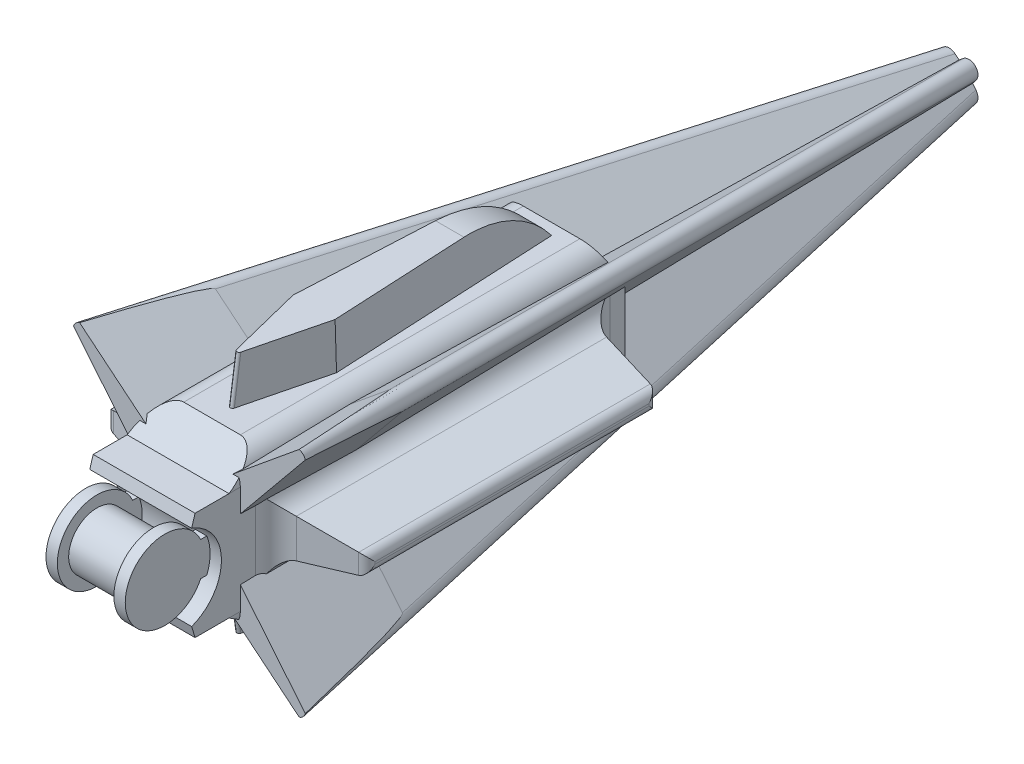
SolidWorks part; units mm, degrees
ref_plane "Front Plane" through (0, 0, 0) normal (0, 0, 1) x (1, 0, 0)
ref_plane "Top Plane" through (0, 0, 0) normal (0, 1, 0) x (1, 0, 0)
ref_plane "Right Plane" through (0, 0, 0) normal (1, 0, 0) x (0, 0, -1)
sketch "Sketch1" plane through (0, 0, 0) normal (1, 0, 0) x (0, 0, -1)
  circle A0 centre (0, 0) radius 3.175
  dimension "D1" = 6.35
extrude "Boss-Extrude1" add sketch "Sketch1" along normal mid plane 6.35
sketch "Sketch2" plane through (3.175, 0, 0) normal (1, 0, 0) x (0, 0, -1)
  circle A0 centre (0, 0) radius 4.445
  dimension "D1" = 8.89
extrude "Boss-Extrude2" add sketch "Sketch2" along normal blind 1.27
mirror "Mirror1" about plane through (0, 0, 0) normal (1, 0, 0) of "Boss-Extrude2"
sketch "Sketch3" plane through (4.445, 0, 0) normal (1, 0, 0) x (0, 0, -1)
  line L1 (0, 1.905) -> (6.35, 1.905)
  line L2 (0, 1.905) -> (0, -1.905)
  line L3 (0, -1.905) -> (6.35, -1.905)
  line L4 (6.35, 1.905) -> (6.35, -1.905)
  point P4 (0, 0)
  dimension "D1" = 3.81
  dimension "D2" = 6.35
extrude "Boss-Extrude3" add sketch "Sketch3" against normal blind 1.27
mirror "Mirror2" about plane through (0, 0, 0) normal (1, 0, 0) of "Boss-Extrude3"
sketch "Sketch4" plane through (-3.175, 0, 0) normal (1, 0, 0) x (0, 0, -1)
  line L0 (1.7375, 4.7736) -> (0, 0) construction
  line L1 (0, 0) -> (5.08, 0) construction
  line L2 (1.7375, 4.7736) -> (2.1185, 6.0436)
  line L3 (2.1185, 6.0436) -> (5.9285, 6.0436)
  line L4 (0, 0) -> (1.7375, -4.7736) construction
  line L5 (5.9285, 6.0436) -> (9.7385, 8.5836)
  line L6 (9.7385, 8.5836) -> (47.8385, 8.5836)
  line L7 (47.8385, 8.5836) -> (50.3785, 3.81)
  line L8 (50.3785, 3.81) -> (50.3785, -3.81)
  line L9 (50.3785, 0) -> (5.08, 0) construction
  line L10 (47.8385, -8.5836) -> (50.3785, -3.81)
  line L11 (9.7385, -8.5836) -> (47.8385, -8.5836)
  line L12 (5.9285, -6.0436) -> (9.7385, -8.5836)
  line L13 (2.1185, -6.0436) -> (5.9285, -6.0436)
  line L14 (1.7375, -4.7736) -> (2.1185, -6.0436)
  arc A0 (1.7375, 4.7736) -> (1.7375, -4.7736) centre (0, 0) cw
  dimension "D1" = 5.08
  dimension "D2" = 140
  dimension "D3" = 1.27
  dimension "D4" = 0.381
  dimension "D5" = 3.81
  dimension "D6" = 3.81
  dimension "D7" = 2.54
  dimension "D8" = 38.1
  dimension "D9" = 7.62
  dimension "D10" = 2.54
extrude "Boss-Extrude4" add sketch "Sketch4" against normal blind 2.54 and the other way blind 8.89
sketch "Sketch5" plane through (0, 0, -50.3785) normal (0, 0, -1) x (-1, 0, 0)
  circle A0 centre (0, 0) radius 3.175
  dimension "D1" = 6.35
extrude "Cut-Extrude1" cut sketch "Sketch5" against normal blind 12.7
fillet "Fillet1" radius 2.54 4 edges at (5.715, -8.5836, -28.7885) (-5.715, -8.5836, -28.7885) (-5.715, 8.5836, -28.7885) (5.715, 8.5836, -28.7885)
sketch "Sketch6" plane through (5.715, 0, 0) normal (1, 0, 0) x (0, 0, -1)
  line L0 (50.3785, -3.81) -> (50.3785, 3.81) construction
  line L1 (11.0085, 2.54) -> (46.5685, 2.54)
  line L2 (11.0085, 2.54) -> (11.0085, -2.54)
  line L3 (11.0085, -2.54) -> (46.5685, -2.54)
  line L4 (46.5685, 2.54) -> (46.5685, -2.54)
  point P4 (11.0085, 0)
  point P6 (50.3785, 0)
  dimension "D1" = 3.81
  dimension "D2" = 5.08
  dimension "D3" = 35.56
extrude "Boss-Extrude5" add sketch "Sketch6" along normal blind 8.89 draft 10
mirror "Mirror3" about plane through (0, 0, 0) normal (1, 0, 0) of "Boss-Extrude5"
fillet "Fillet2" radius 1.016 8 edges at (-14.605, -0.9725, -28.7885) (-14.605, 0, -45.0009) (-14.605, 0.9725, -28.7885) (-14.605, 0, -12.576) (14.605, 0.9725, -28.7885) (14.605, 0, -45.0009) (14.605, -0.9725, -28.7885) (14.605, 0, -12.576)
fillet "Fillet3" radius 2.54 8 edges at (5.715, -2.54, -28.7885) (5.715, 0, -11.0085) (5.715, 0, -46.5685) (5.715, 2.54, -28.7885) (-5.715, 0, -11.0085) (-5.715, 0, -46.5685) (-5.715, -2.54, -28.7885) (-5.715, 2.54, -28.7885)
sketch "Sketch7" plane through (0, 8.5836, 0) normal (0, 1, 0) x (1, 0, 0)
  line L0 (0, 9.7385) -> (0, 47.8385) construction
  line L1 (3.175, 9.7385) -> (-3.175, 9.7385) construction
  line L2 (3.175, 47.8385) -> (-3.175, 47.8385) construction
  line L3 (-1.27, 46.5685) -> (1.27, 46.5685)
  line L4 (1.27, 46.5685) -> (2.54, 21.1685)
  line L5 (2.54, 21.1685) -> (0, 11.0085)
  line L6 (0, 11.0085) -> (-2.54, 21.1685)
  line L7 (-2.54, 21.1685) -> (-1.27, 46.5685)
  point P8 (0, 46.5685)
  dimension "D1" = 2.54
  dimension "D2" = 1.27
  dimension "D3" = 1.27
  dimension "D4" = 2.54
  dimension "D5" = 25.4
extrude "Boss-Extrude6" add sketch "Sketch7" along normal blind 5.08 draft 2
mirror "Mirror4" about plane through (0, 0, 0) normal (0, 1, 0) of "Boss-Extrude6"
fillet "Fillet4" radius 0.254 2 edges at (0, -11.1236, -11.3742) (0, 11.1236, -11.3742)
fillet "Fillet5" radius 12.7 2 edges at (0, -13.6636, -46.3911) (0, 13.6636, -46.3911)
ref_plane "Plane1" through (0, 0, -19.8985) normal (0, 0, -1) x (-1, 0, 0)
sketch "Sketch8" plane through (0, 0, -19.8985) normal (0, 0, -1) x (-1, 0, 0)
  line L0 (0, -13.6636) -> (0, 13.6636) construction
  line L1 (-1.6004, 13.6636) -> (1.6004, 13.6636) construction
  line L2 (0, 0) -> (15.4727, 0) construction
  line L3 (0, 3.175) -> (17.78, 17.78)
  line L4 (17.78, 17.78) -> (3.175, 0)
  line L5 (0, 0) -> (17.78, 17.78) construction
  line L6 (0, 0) -> (-17.78, 17.78) construction
  line L7 (-17.78, 17.78) -> (-3.175, 0)
  line L8 (0, 3.175) -> (-17.78, 17.78)
  line L9 (0, 0) -> (-17.78, -17.78) construction
  line L10 (0, 0) -> (17.78, -17.78) construction
  line L11 (0, -3.175) -> (-17.78, -17.78)
  line L12 (-17.78, -17.78) -> (-3.175, 0)
  line L13 (17.78, -17.78) -> (3.175, 0)
  line L14 (0, -3.175) -> (17.78, -17.78)
  circle A0 centre (0, 0) radius 3.175 construction
  dimension "D1" = 45
  dimension "D2" = 17.78
extrude "Boss-Extrude7" add sketch "Sketch8" along normal blind 73.66 draft 1 and the other way blind 12.7 draft 1
fillet "Fillet6" radius 1.016 4 edges at (-13.1211, -13.1211, -56.7285) (-13.1211, 13.1211, -56.7285) (13.1211, -13.1211, -56.7285) (13.1211, 13.1211, -56.7285)
